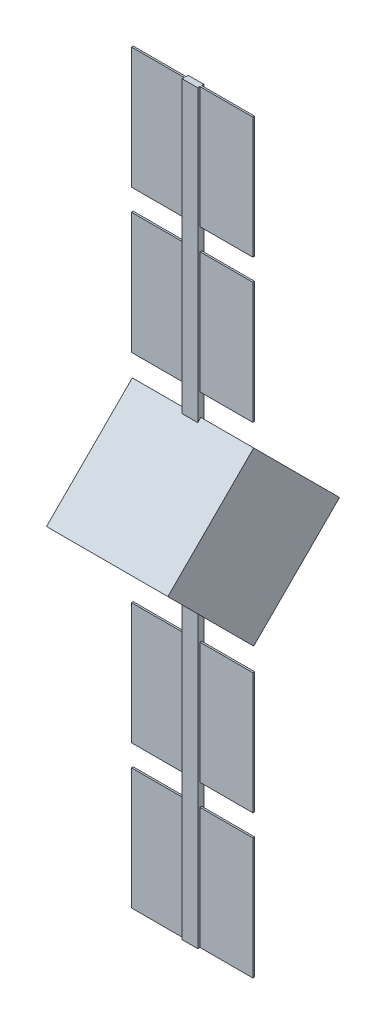
SolidWorks part; units mm, degrees
ref_plane "Piano frontale" through (0, 0, 0) normal (0, 0, 1) x (1, 0, 0)
ref_plane "Piano superiore" through (0, 0, 0) normal (0, 1, 0) x (1, 0, 0)
ref_plane "Piano destro" through (0, 0, 0) normal (1, 0, 0) x (0, 0, -1)
sketch "Schizzo1" plane through (0, 0, 0) normal (0, 1, 0) x (1, 0, 0)
  line L1 (350, -350) -> (-350, -350)
  line L2 (350, -350) -> (350, 350)
  line L3 (350, 350) -> (-350, 350)
  line L4 (-350, -350) -> (-350, 350)
  line L5 (350, -350) -> (-350, 350) construction
  line L6 (350, 350) -> (-350, -350) construction
  point P0 (0, 0)
  dimension "D1" = 700
extrude "Estrusione-Estrusione1" add sketch "Schizzo1" along normal mid plane 700
ref_axis "Asse x" through (-713.3024, 0, 0) along (1, 0, 0)
ref_axis "Asse y" through (0, 2248.9247, 0) along (0, -1, 0)
ref_axis "Asse z" through (0, 0, -730.5603) along (0, 0, 1)
ref_plane "Piano1" through (0, 0, 0) normal (-0.7071, 0, 0.7071) x (0, -1, 0)
ref_plane "Piano2" through (0, 0, 0) normal (0.7071, 0, 0.7071) x (0, -1, 0)
ref_axis "Assiale" through (1589.8132, 0, -1589.8132) along (-0.7071, 0, 0.7071)
sketch "Schizzo4" plane through (0, 0, 0) normal (-0.7071, 0, 0.7071) x (0, -1, 0)
  line L1 (45, 17.5) -> (-45, 17.5)
  line L2 (45, 17.5) -> (45, -17.5)
  line L3 (45, -17.5) -> (-45, -17.5)
  line L4 (-45, 17.5) -> (-45, -17.5)
  line L5 (45, 17.5) -> (-45, -17.5) construction
  line L6 (45, -17.5) -> (-45, 17.5) construction
  point P0 (0, 0)
  dimension "D1" = 90
  dimension "D2" = 35
extrude "Estrusione-Estrusione2" add sketch "Schizzo4" along normal mid plane 4300
sketch "Schizzo6" plane through (0, 0, 0) normal (0.7071, 0, 0.7071) x (0, -1, 0)
  line L0 (0, 2248.3354) -> (0, -2286.6178) construction
  line L1 (350, -624.9747) -> (-350, -624.9747)
  line L2 (350, -624.9747) -> (350, -1324.9747)
  line L3 (350, -1324.9747) -> (-350, -1324.9747)
  line L4 (-350, -624.9747) -> (-350, -1324.9747)
  line L5 (350, -624.9747) -> (-350, -1324.9747) construction
  line L6 (350, -1324.9747) -> (-350, -624.9747) construction
  line L7 (45, -494.9747) -> (350, -494.9747) construction
  point P0 (0, -974.9747)
  dimension "D1" = 700
  dimension "D2" = 130
extrude "Estrusione-Estrusione3" add sketch "Schizzo6" along normal mid plane 10
sketch "Schizzo7" plane through (0, 0, 0) normal (0.7071, 0, 0.7071) x (0, -1, 0)
  line L0 (0, 2248.3354) -> (0, -2286.6178) construction
  line L1 (350, -2150) -> (-350, -2150)
  line L2 (350, -2150) -> (350, -1450)
  line L3 (350, -1450) -> (-350, -1450)
  line L4 (-350, -2150) -> (-350, -1450)
  line L5 (350, -2150) -> (-350, -1450) construction
  line L6 (350, -1450) -> (-350, -2150) construction
  line L7 (350, -1324.9747) -> (350, -624.9747) construction
  line L8 (350, -1324.9747) -> (350, -624.9747) construction
  line L9 (45, -2150) -> (-45, -2150) construction
  point P0 (0, -1800)
extrude "Estrusione-Estrusione4" add sketch "Schizzo7" along normal mid plane 10
mirror "Specchia1" about plane through (0, 0, 0) normal (-0.7071, 0, 0.7071) of "Estrusione-Estrusione4", "Estrusione-Estrusione3"
move or copy body "Corpo-Sposta/copia1" bodies to move or copy 105 copy no rotation origin (0, 0, 0) rotation axis (0.3574, -0.3574, 0.8629) rotation angle 98.421
